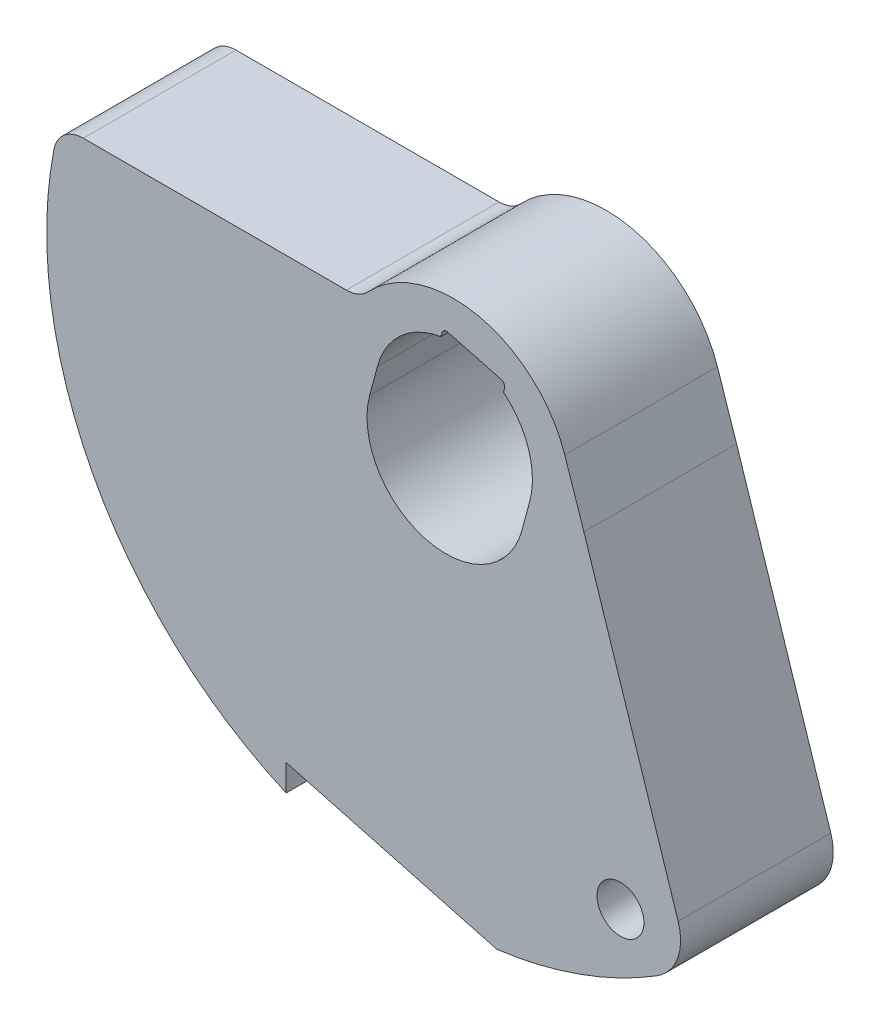
SolidWorks part; units mm, degrees
ref_plane "Front Plane" through (0, 0, 0) normal (0, 0, 1) x (1, 0, 0)
ref_plane "Top Plane" through (0, 0, 0) normal (0, 1, 0) x (1, 0, 0)
ref_plane "Right Plane" through (0, 0, 0) normal (1, 0, 0) x (0, 0, -1)
sketch "Sketch1" plane through (0, 0, 0) normal (0, 0, 1) x (1, 0, 0)
  line L0 (0, 40.7088) -> (0, -42.4788) construction
  line L1 (50.0011, 0) -> (-47.9361, 0) construction
  line L2 (0, 0) -> (4.815, 17.9697) construction
  line L3 (-7.4706, 2.0017) -> (6.4814, -1.7367) construction
  line L4 (-7.0762, 3.4738) -> (6.8758, -0.2646) construction
  line L5 (-3.8765, 1.0387) -> (-3.482, 2.5108)
  line L6 (4.2709, 0.4334) -> (3.8765, -1.0387)
  line L7 (-5.0653, 5.08) -> (-18.4566, 5.08)
  line L8 (6.0531, 3.3717) -> (7.0281, 0.4672)
  line L9 (12.9403, -3.6173) -> (17.147, -10.9034)
  line L10 (0, 0) -> (5.8427, -10.1199) construction
  line L11 (0, 0) -> (43.883, -11.7584) construction
  line L12 (8.89, 40.7088) -> (8.89, -42.4788) construction
  line L13 (50.0011, -15.24) -> (-47.9361, -15.24) construction
  line L14 (-1.0387, -3.8765) -> (-9.0244, -1.7367) construction
  line L15 (-8.128, -17.2812) -> (-8.128, -18.6236)
  line L16 (-8.128, -17.2812) -> (2.5931, -20.1539)
  line L17 (2.8088, 5.0851) -> (0.11, 5.8082)
  line L18 (1.4594, 5.4467) -> (-6.5263, 7.5864) construction
  line L21 (2.9359, 4.578) -> (2.9884, 4.774)
  line L24 (-0.2536, 5.4326) -> (-0.2011, 5.6286)
  arc A0 (-3.8765, 1.0387) -> (3.8765, -1.0387) centre (0, 0) ccw
  arc A1 (6.1601, -0.0728) -> (6.1791, 0) centre (0.3944, 1.4721) ccw
  arc A2 (4.2709, 0.4334) -> (2.9359, 4.578) centre (0.3944, 1.4721) ccw
  arc A3 (7.0281, 0.4672) -> (12.6001, -3.4269) centre (12.446, 2.286) ccw
  arc A4 (6.0531, 3.3717) -> (-3.9548, 5.5602) centre (0.3944, 1.4721) ccw
  arc A5 (-19.953, 3.8443) -> (-8.128, -18.6236) centre (0, 0) ccw
  arc A6 (12.6001, -3.4269) -> (12.9403, -3.6173) centre (12.6104, -3.8078) cw
  arc A7 (2.5931, -20.1539) -> (17.147, -10.9034) centre (0, 0) ccw
  arc A8 (-18.4566, 5.08) -> (-19.953, 3.8443) centre (-18.4566, 3.556) ccw
  arc A9 (-5.0653, 5.08) -> (-3.9548, 5.5602) centre (-5.0653, 6.604) ccw
  circle A10 centre (8.89, -15.24) radius 1.1938
  arc A11 (-0.2536, 5.4326) -> (-3.482, 2.5108) centre (0.3944, 1.4721) ccw
  arc A12 (2.8088, 5.0851) -> (2.9884, 4.774) centre (2.7431, 4.8397) cw
  arc A13 (-0.2011, 5.6286) -> (0.11, 5.8082) centre (0.0443, 5.5629) cw
  point P35 (-9.9822, 40.7088)
  point P36 (-9.9822, -42.4788)
  point P48 (1.5947, -0.4273)
  point P50 (6.4097, 17.5424)
  point P51 (-1.5947, 0.4273)
  point P52 (3.2202, 18.397)
  point P60 (-8.382, -16.9501)
  dimension "D1" = 8.0264
  dimension "D4" = 11.938
  dimension "D6" = 11.43
  dimension "D11" = 40.64
  dimension "D12" = 0.381
  dimension "D16" = 1.524
  dimension "D17" = 1.524
  dimension "D20" = 2.3876
  dimension "D24" = 0.254
  dimension "D2" = 15
  dimension "D5" = 5.08
  dimension "D7" = 2.286
  dimension "D8" = 12.446
  dimension "D9" = 60
  dimension "D10" = 9.398
  dimension "D13" = 15
  dimension "D14" = 18.796
  dimension "D15" = 8.128
  dimension "D22" = 3.302
  dimension "D23" = 1.651
  dimension "D3" = 1.524
  dimension "D18" = 8.89
  dimension "D19" = 15.24
  dimension "D21" = 9.652
extrude "Boss-Extrude1" add sketch "Sketch1" against normal blind 7.7724 contours A9 L7 A8 A5 L15 L16 A7 L9 A6 A3 L8 A4 A10 A2 L6 A0 L5 region at (-3.0469, -7.1935, 0)
sketch "Sketch2" plane through (0, 0, 0) normal (0, 0, 1) x (1, 0, 0)
  line L0 (7.0281, 0.4672) -> (12.4084, -16.0914)
  arc A0 (2.5931, -20.1539) -> (17.147, -10.9034) centre (0, 0) ccw construction
  dimension "D1" = 72
extrude "Cut-Extrude1" cut sketch "Sketch2" against normal through all and the other way through all
fillet "Fillet1" radius 2.54 1 edges at (12.4084, -16.0914, -3.8862)
